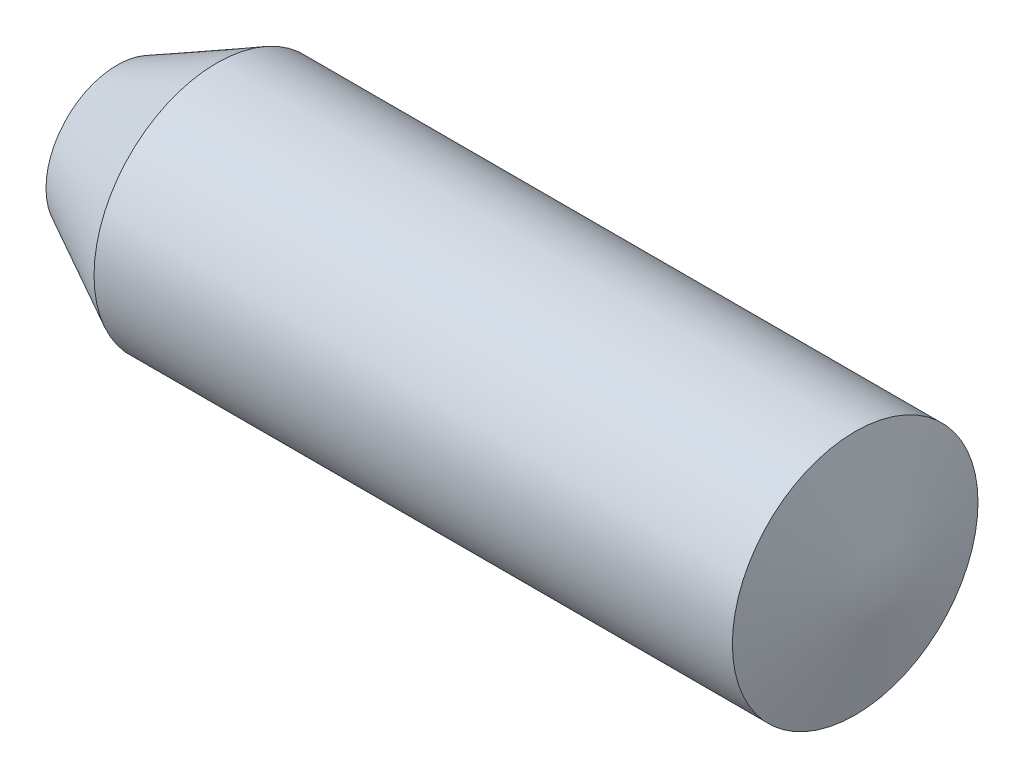
SolidWorks part; units mm, degrees
ref_plane "Front Plane" through (0, 0, 0) normal (0, 0, 1) x (1, 0, 0)
ref_plane "Top Plane" through (0, 0, 0) normal (0, 1, 0) x (1, 0, 0)
ref_plane "Right Plane" through (0, 0, 0) normal (1, 0, 0) x (0, 0, -1)
sketch "Sketch1" plane through (0, 0, 0) normal (0, 0, 1) x (1, 0, 0)
  line L0 (0, 0) -> (1828.8, 0) construction
  line L1 (0, 0) -> (0, 169.0969)
  line L2 (0, 169.0969) -> (237.2457, 292.1)
  line L3 (237.2457, 292.1) -> (1755.5085, 292.1)
  line L4 (1755.5085, 292.1) -> (1828.8, 0)
  line L5 (0, 0) -> (1828.8, 0)
  point P5 (1755.5085, 292.1)
  dimension "D1" = 1828.8
  dimension "D2" = 584.2
revolve "Revolve1" add sketch "Sketch1" angle 360 about L0
